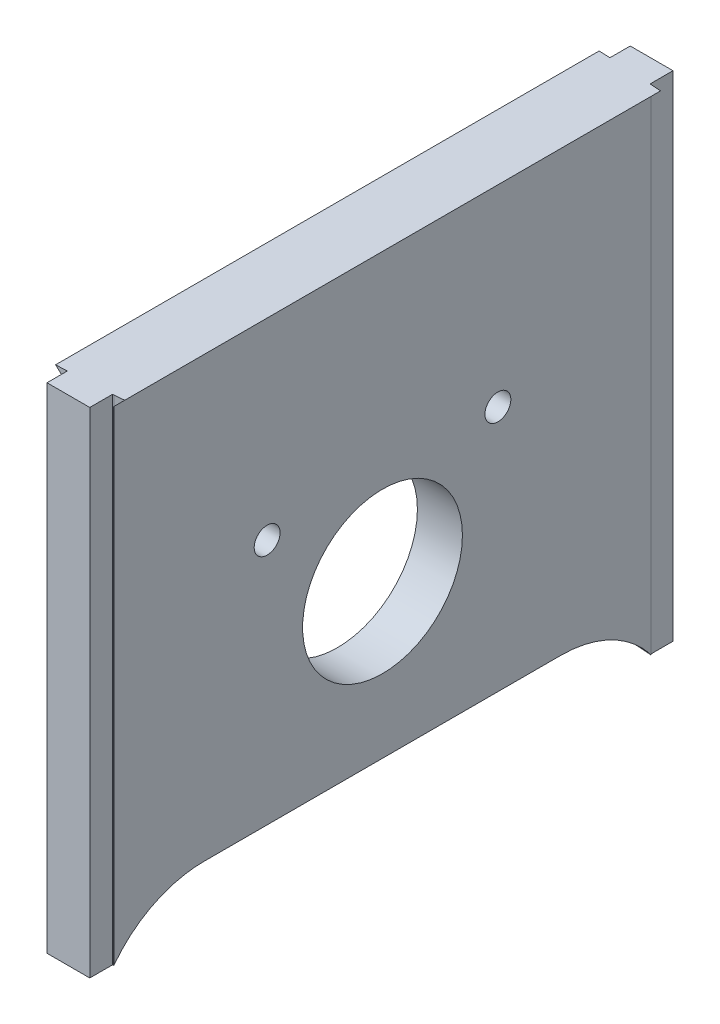
SolidWorks part; units mm, degrees
material "PLA"
ref_plane "Front Plane" through (0, 0, 0) normal (0, 0, 1) x (1, 0, 0)
ref_plane "Top Plane" through (0, 0, 0) normal (0, 1, 0) x (1, 0, 0)
ref_plane "Right Plane" through (0, 0, 0) normal (1, 0, 0) x (0, 0, -1)
sketch "Sketch1" plane through (0, 0, 0) normal (1, 0, 0) x (0, 0, -1)
  line L0 (-17.25, 0) -> (-17.25, -67.25)
  line L1 (17.25, 0) -> (17.25, -67.25)
  line L2 (-17.25, -67.25) -> (17.25, -67.25)
  arc A0 (17.25, 0) -> (-17.25, 0) centre (0, 0) ccw
  circle A1 centre (0, 0) radius 4.1
  circle A2 centre (0, 0) radius 8.125 construction
  circle A3 centre (0, 8.125) radius 1.15
  circle A4 centre (8.125, 0) radius 1.15
  circle A5 centre (-8.125, 0) radius 1.15
  circle A6 centre (0, -8.125) radius 1.15
  dimension "D1" = 34.5
  dimension "D4" = 8.2
  dimension "D5" = 16.25
  dimension "D6" = 2.3
  dimension "D2" = 67.25
  dimension "D3" = 67.25
extrude "Boss-Extrude1" add sketch "Sketch1" along normal blind 3.5
ref_plane "Plane1" through (0, 0, 0) normal (0, -1, 0) x (-1, 0, 0)
ref_plane "Plane2" through (29.7, 0, 0) normal (-1, 0, 0) x (0, 0, 1)
sketch "Sketch2" plane through (0, 0, 0) normal (0, -1, 0) x (-1, 0, 0)
  line L0 (0, -17.25) -> (-59.4, -17.25) construction
  line L1 (-29.7, 0) -> (-29.7, -28) construction
  line L3 (-59.4, -17.25) -> (-59.4, -20.25)
  line L4 (0, -17.25) -> (0, -20.25)
  line L6 (-29.7, -28) -> (-17.6897, -27.7644) construction
  line L7 (-17.6897, -27.7644) -> (-9.1109, -26.529) construction
  line L8 (-9.1109, -26.529) -> (-3.2086, -24.1613) construction
  line L9 (-3.2086, -24.1613) -> (-1.3201, -22.8861) construction
  line L10 (-1.3201, -22.8861) -> (-0.3051, -21.5079) construction
  line L11 (-0.3051, -21.5079) -> (-0.1375, -21.1541) construction
  line L12 (-0.1375, -21.1541) -> (0, -20.25) construction
  line L13 (-3.5, -17.25) -> (-3.7359, -19.9547)
  line L14 (-55.9, -17.25) -> (-55.6641, -19.9547)
  line L15 (-55.9, -17.25) -> (-59.4, -17.25)
  line L17 (0, -17.25) -> (-3.5, -17.25)
  arc A0 (0, -20.25) -> (-1.3201, -22.8861) centre (-4.0147, -19.8881) cw
  arc A1 (-1.3201, -22.8861) -> (-9.1109, -26.529) centre (-11.2153, -11.8765) cw
  arc A2 (-29.7, -28) -> (-9.1109, -26.529) centre (-29.7, 116.8281) ccw
  arc A3 (-29.7, -24.2523) -> (-9.3648, -22.779) centre (-29.7, 116.8281) ccw
  arc A4 (-3.8286, -20.1061) -> (-9.3648, -22.779) centre (-11.2153, -11.8765) cw
  arc A5 (-3.7359, -19.9547) -> (-3.8286, -20.1061) centre (-4.0147, -19.8881) cw
  arc A6 (-29.7, -28) -> (-50.2891, -26.529) centre (-29.7, 116.8281) cw
  arc A7 (-58.0799, -22.8861) -> (-50.2891, -26.529) centre (-48.1847, -11.8765) ccw
  arc A8 (-59.4, -20.25) -> (-58.0799, -22.8861) centre (-55.3853, -19.8881) ccw
  arc A9 (-55.6641, -19.9547) -> (-55.5714, -20.1061) centre (-55.3853, -19.8881) ccw
  arc A10 (-55.5714, -20.1061) -> (-50.0352, -22.779) centre (-48.1847, -11.8765) ccw
  arc A11 (-29.7, -24.2523) -> (-50.0352, -22.779) centre (-29.7, 116.8281) cw
  dimension "D1" = 59.4
extrude "Boss-Extrude2" add sketch "Sketch2" along normal blind 67.25
mirror "Mirror2" about plane through (29.7, 0, 0) normal (-1, 0, 0) of "Boss-Extrude1"
sketch "Sketch3" plane through (0, 0, 0) normal (-1, 0, 0) x (0, 0, 1)
  line L0 (17.25, 0) -> (32.7486, -8.9481)
  line L1 (-1.925, 0) -> (1.925, 0) construction
  line L2 (32.7486, -8.9481) -> (32.7486, 0)
  line L3 (32.7486, 0) -> (17.25, 0)
  arc A0 (17.25, 0) -> (-17.25, 0) centre (0, 0) ccw construction
  dimension "D1" = 30
extrude "Cut-Extrude1" cut sketch "Sketch3" against normal through all
ref_plane "Plane3" through (0, 0, 0) normal (0, 0, -1) x (-1, 0, 0)
mirror "Mirror3" about plane through (0, 0, 0) normal (0, 0, -1) of "Cut-Extrude1", "Boss-Extrude2"
sketch "Sketch4" plane through (0, 0, 0) normal (-1, 0, 0) x (0, 0, 1)
  line L0 (-20.25, -63.75) -> (-20.25, -1.7321) construction
  line L1 (-13.25, -13.5) -> (13.25, -13.5)
  line L2 (-13.25, -13.5) -> (-13.25, -60.75)
  line L3 (-13.25, -60.75) -> (13.25, -60.75)
  line L4 (13.25, -13.5) -> (13.25, -60.75)
  line L5 (20.25, -63.75) -> (20.25, -1.7321) construction
  line L6 (20.25, -67.25) -> (-19.5262, -67.25) construction
  dimension "D1" = 7
  dimension "D2" = 7
  dimension "D3" = 13.5
  dimension "D4" = 6.5
extrude "Cut-Extrude2" cut sketch "Sketch4" against normal blind 3.5
sketch "Sketch6" plane through (0, 0, 0) normal (-1, 0, 0) x (0, 0, 1)
  line L8 (-15.75, -63.25) -> (15.75, -63.25)
  line L9 (-15.75, -11) -> (-15.75, -63.25)
  line L10 (15.75, -63.25) -> (15.75, -11)
  line L11 (15.75, -11) -> (-15.75, -11)
  line L12 (-15.75, -63.25) -> (15.75, -63.25)
  line L13 (-15.75, -11) -> (-15.75, -63.25)
  line L14 (15.75, -63.25) -> (15.75, -11)
  line L15 (15.75, -11) -> (-15.75, -11)
  dimension "D1" = 2.5
extrude "Boss-Extrude3" add sketch "Sketch6" along normal blind 2
chamfer "Chamfer2" distance 2 angle 45 4 edges at (-2, -63.25, 0) (-2, -37.125, 15.75) (-2, -37.125, -15.75) (-2, -11, 0)
sketch "Sketch7" plane through (0, 0, 0) normal (1, 0, 0) x (0, 0, -1)
  line L4 (-13.25, -60.75) -> (13.25, -60.75)
  line L5 (13.25, -60.75) -> (13.25, -13.5)
  line L6 (13.25, -13.5) -> (-13.25, -13.5)
  line L7 (-13.25, -13.5) -> (-13.25, -60.75)
  line L8 (-13.25, -60.75) -> (13.25, -60.75)
  line L9 (13.25, -60.75) -> (13.25, -13.5)
  line L10 (13.25, -13.5) -> (-13.25, -13.5)
  line L11 (-13.25, -13.5) -> (-13.25, -60.75)
  dimension "D1" = 0
extrude "Cut-Extrude3" cut sketch "Sketch7" against normal blind 0.8
sketch "Sketch8" plane through (-2, 0, 0) normal (-1, 0, 0) x (0, 0, 1)
  line L0 (15.75, -63.25) -> (15.75, -11) construction
  line L1 (-10.6511, -32.25) -> (10.75, -32.25)
  line L2 (-10.6511, -32.25) -> (-10.6511, -38.75)
  line L3 (-10.6511, -38.75) -> (10.75, -38.75)
  line L4 (10.75, -32.25) -> (10.75, -38.75)
  line L5 (-15.75, -11) -> (-15.75, -63.25) construction
  line L6 (15.75, -11) -> (7.6086, -11) construction
  line L7 (-15.75, -63.25) -> (15.75, -63.25) construction
  dimension "D1" = 5
  dimension "D2" = 5.0989
  dimension "D3" = 21.25
  dimension "D4" = 24.5
extrude "Cut-Extrude4" cut sketch "Sketch8" against normal up to next
sketch "Sketch9" plane through (59.4, 0, 0) normal (1, 0, 0) x (0, 0, -1)
  circle A0 centre (0, -49.64) radius 7.1
  dimension "D1" = 14.2
extrude "Cut-Extrude5" cut sketch "Sketch9" against normal up to next
ref_plane "Plane4" through (0, -19.75, 0) normal (0, -1, 0) x (-1, 0, 0)
sketch "Sketch10" plane through (0, -19.75, 0) normal (0, -1, 0) x (-1, 0, 0)
  line L0 (-55.6641, -19.9547) -> (-55.9, -17.25) construction
  line L1 (-3.5, -17.25) -> (-3.7359, -19.9547) construction
  line L3 (-3.5, -17.25) -> (-3.5, 17.25) construction
  line L6 (-3.5, 17.25) -> (-3.7359, 19.9547) construction
  line L7 (-55.9, -17.25) -> (-55.9, 17.25) construction
  line L8 (-55.6641, 19.9547) -> (-55.9, 17.25) construction
  line L9 (-55.6641, -19.9547) -> (-55.9, -17.25)
  line L10 (-3.5, -17.25) -> (-3.7359, -19.9547)
  line L11 (-3.5, -17.25) -> (-3.5, -12.56)
  line L12 (-3.5, 17.25) -> (-3.7359, 19.9547)
  line L13 (-55.9, -17.25) -> (-55.9, 17.25)
  line L14 (-55.6641, 19.9547) -> (-55.9, 17.25)
  line L15 (-18.2613, -12.36) -> (-18.2613, -12.56) construction
  line L16 (-12.72, -12.36) -> (-25.62, -12.36) construction
  line L17 (-3.5, -12.56) -> (-34.52, -12.56)
  line L18 (-34.52, -12.56) -> (-34.52, 12.56)
  line L19 (-3.5, 12.56) -> (-3.5, 17.25)
  line L43 (-34.52, 12.56) -> (-3.5, 12.56)
  line L45 (-25.62, 12.36) -> (-12.72, 12.36) construction
  line L46 (-34.52, 5) -> (-34.52, 13.1992) construction
  line L47 (-31.62, 5) -> (-35.82, 5) construction
  line L48 (-34.32, 6.7) -> (-34.32, 5.6557) construction
  arc A0 (-55.6641, -19.9547) -> (-55.5714, -20.1061) centre (-55.3853, -19.8881) ccw construction
  arc A1 (-50.0352, -22.779) -> (-9.3648, -22.779) centre (-29.7, 116.8281) ccw construction
  arc A2 (-55.5714, -20.1061) -> (-50.0352, -22.779) centre (-48.1847, -11.8765) ccw construction
  arc A3 (-9.3648, -22.779) -> (-3.8286, -20.1061) centre (-11.2153, -11.8765) ccw construction
  arc A4 (-3.8286, -20.1061) -> (-3.7359, -19.9547) centre (-4.0147, -19.8881) ccw construction
  arc A5 (-3.7359, 19.9547) -> (-3.8286, 20.1061) centre (-4.0147, 19.8881) ccw construction
  arc A6 (-3.8286, 20.1061) -> (-9.3648, 22.779) centre (-11.2153, 11.8765) ccw construction
  arc A7 (-9.3648, 22.779) -> (-50.0352, 22.779) centre (-29.7, -116.8281) ccw construction
  arc A8 (-55.5714, 20.1061) -> (-55.6641, 19.9547) centre (-55.3853, 19.8881) ccw construction
  arc A9 (-50.0352, 22.779) -> (-55.5714, 20.1061) centre (-48.1847, 11.8765) ccw construction
  arc A30 (-55.6641, -19.9547) -> (-55.5714, -20.1061) centre (-55.3853, -19.8881) ccw
  arc A31 (-50.0352, -22.779) -> (-9.3648, -22.779) centre (-29.7, 116.8281) ccw
  arc A32 (-55.5714, -20.1061) -> (-50.0352, -22.779) centre (-48.1847, -11.8765) ccw
  arc A33 (-9.3648, -22.779) -> (-3.8286, -20.1061) centre (-11.2153, -11.8765) ccw
  arc A34 (-3.8286, -20.1061) -> (-3.7359, -19.9547) centre (-4.0147, -19.8881) ccw
  arc A35 (-3.7359, 19.9547) -> (-3.8286, 20.1061) centre (-4.0147, 19.8881) ccw
  arc A36 (-3.8286, 20.1061) -> (-9.3648, 22.779) centre (-11.2153, 11.8765) ccw
  arc A37 (-9.3648, 22.779) -> (-50.0352, 22.779) centre (-29.7, -116.8281) ccw
  arc A38 (-55.5714, 20.1061) -> (-55.6641, 19.9547) centre (-55.3853, 19.8881) ccw
  arc A39 (-50.0352, 22.779) -> (-55.5714, 20.1061) centre (-48.1847, 11.8765) ccw
  dimension "D1" = 0.2
  dimension "D2" = 0.2
  dimension "D3" = 0.2
extrude "Boss-Extrude4" add sketch "Sketch10" along normal blind 3.5
sketch "Sketch11" plane through (0, -23.25, 0) normal (0, -1, 0) x (-1, 0, 0)
  line L0 (-36.07, -6.9) -> (-40.07, -6.9) construction
  line L2 (-36.07, -6.9) -> (-36.07, -24.1084) construction
  line L3 (-40.07, -6.9) -> (-40.07, -24.1084) construction
  line L5 (-36.07, -24.1084) -> (-40.07, -24.1084)
  line L6 (-36.07, -24.1084) -> (-36.07, 25.609)
  line L7 (-36.07, 25.609) -> (-40.07, 25.609)
  line L8 (-40.07, -24.1084) -> (-40.07, 25.609)
  arc A0 (-50.0352, -22.779) -> (-41.07, -23.7934) centre (-29.7, 116.8281) ccw construction
  dimension "D1" = 4
extrude "Boss-Extrude5" add sketch "Sketch11" along normal blind 40
sketch "Sketch12" plane through (40.07, 0, 0) normal (1, 0, 0) x (0, 0, -1)
  circle A0 centre (0, -49.64) radius 7.1
extrude "Cut-Extrude6" cut sketch "Sketch12" against normal blind 10
chamfer "Chamfer3" distance 1 angle 45 1 edges at (36.07, -23.25, 0)
chamfer "Chamfer4" distance 1 angle 45 1 edges at (40.07, -23.25, 0)
sketch "Sketch13" plane through (59.4, 0, 0) normal (1, 0, 0) x (0, 0, -1)
  circle A0 centre (0, -49.64) radius 9
  circle A1 centre (0, -49.64) radius 5.5
  dimension "D1" = 18
  dimension "D2" = 11
extrude "Boss-Extrude6" add sketch "Sketch13" along normal blind 1.5
sketch "Sketch16" plane through (60.9, 0, 0) normal (1, 0, 0) x (0, 0, -1)
  circle A0 centre (0, -49.64) radius 9
extrude "Boss-Extrude7" add sketch "Sketch16" along normal blind 1
fillet "Fillet2" radius 1 1 edges at (61.9, -49.64, -9)
ref_plane "Plane5" through (0, 0, 20.25) normal (0, 0, -1) x (-1, 0, 0)
sketch "Sketch17" plane through (0, 0, 20.25) normal (0, 0, -1) x (-1, 0, 0)
  line L0 (-59.4, -67.25) -> (-55.9, -67.25) construction
  line L1 (-59.4, -67.25) -> (-59.4, -70.75) construction
  line L3 (-55.9, -67.25) -> (-59.4, -70.75) construction
  line L4 (-59.4, -67.25) -> (-59.65, -67.25) construction
  line L5 (-59.4, -70.75) -> (-59.65, -71) construction
  line L6 (-59.65, -71) -> (-59.65, -105.91) construction
  line L7 (-59.4, -67.25) -> (-59.4, -63.75) construction
  line L8 (-59.4, -63.75) -> (-64.5645, -68.9145) construction
  line L9 (-59.65, -105.91) -> (-63.15, -105.91)
  line L10 (-63.15, -105.91) -> (-63.15, -67.5)
  line L11 (-63.15, -67.5) -> (-59.4, -63.75)
  line L12 (-59.4, -63.75) -> (-59.4, -67.25)
  line L13 (-59.4, -67.25) -> (-55.9, -67.25)
  line L14 (-55.9, -67.25) -> (-59.65, -71)
  line L15 (-59.65, -71) -> (-59.65, -105.91)
  dimension "D1" = 3.5
  dimension "D2" = 3.5
  dimension "D3" = 0.25
  dimension "D4" = 3.5
  dimension "D5" = 45
  dimension "D6" = 3.5
sketch "Sketch18" plane through (55.9, 0, 0) normal (-1, 0, 0) x (0, 0, 1)
  circle A0 centre (0, -49.64) radius 9
  circle A1 centre (0, -49.64) radius 7.1
  circle A2 centre (0, -49.64) radius 7.1
  dimension "D2" = 18
  dimension "D1" = 0
extrude "Boss-Extrude8" add sketch "Sketch18" along normal blind 0.5
chamfer "Chamfer5" distance 0.5 angle 45 1 edges at (55.9, -49.64, 9)
extrude "Boss-Extrude9" add sketch "Sketch17" along normal blind 40.5
sketch "Sketch19" plane through (63.15, 0, 0) normal (1, 0, 0) x (0, 0, -1)
  line L0 (-17.7, -88.21) -> (-20.25, -85.66)
  line L1 (-20.25, -85.66) -> (-20.25, -105.91)
  line L2 (20.25, -105.91) -> (-20.25, -105.91) construction
  line L3 (0, -105.91) -> (0, -88.21) construction
  line L4 (-20.25, -67.5) -> (-20.25, -105.91) construction
  line L5 (17.7, -88.21) -> (20.25, -85.66)
  line L6 (-20.25, -105.91) -> (0, -105.91)
  line L7 (20.25, -67.5) -> (20.25, -105.91) construction
  line L8 (0, -105.91) -> (20.25, -105.91)
  line L9 (20.25, -105.91) -> (20.25, -85.66)
  arc A0 (-17.7, -88.21) -> (17.7, -88.21) centre (0, -88.21) ccw
  line M5 (-20.25, -67.5) -> (-20.25, -105.91)
  line M6 (-20.25, -105.91) -> (20.25, -105.91)
  line M7 (20.25, -105.91) -> (20.25, -67.5)
  dimension "D1" = 17.7
  dimension "D2" = 45
  dimension "D3" = 45
extrude "Cut-Extrude8" cut sketch "Sketch19" against normal up to next contours A0 L0 M5 M6 | A0 L5 M6 M7
chamfer "Chamfer6" distance 1.5 angle 45 1 edges at (59.4, -49.64, 9)
sketch "Sketch20" plane through (63.15, 0, 0) normal (1, 0, 0) x (0, 0, -1)
  line L0 (0, -49.64) -> (0, -88.21) construction
  circle A0 centre (0, -88.21) radius 7.1
  dimension "D2" = 14.2
  dimension "D1" = 38.57
extrude "Cut-Extrude9" cut sketch "Sketch20" against normal up to next
sketch "Sketch21" plane through (0, 0, 0) normal (-1, 0, 0) x (0, 0, 1)
  circle A0 centre (0, 8.125) radius 1.5
  circle A1 centre (8.125, 0) radius 1.5
  circle A2 centre (0, -8.125) radius 1.5
  circle A3 centre (-8.125, 0) radius 1.5
  dimension "D1" = 3
extrude "Boss-Extrude10" add sketch "Sketch21" against normal blind 3.5
mirror "Mirror4" about plane through (29.7, 0, 0) normal (-1, 0, 0) of "Cut-Extrude9", "Cut-Extrude8", "Boss-Extrude9"
sketch "Sketch22" plane through (-2, 0, 0) normal (-1, 0, 0) x (0, 0, 1)
  circle A0 centre (0, -49.64) radius 3.75
  dimension "D1" = 7.5
extrude "Cut-Extrude10" cut sketch "Sketch22" against normal up to next
sketch "Sketch23" plane through (-0.8, 0, 0) normal (1, 0, 0) x (0, 0, -1)
  line L65 (10.8, -38.89) -> (7, -38.89)
  line L66 (10.8, -32.115) -> (10.8, -38.89)
  line L67 (9.303, -32.115) -> (10.8, -32.115)
  line L68 (9.4423, -31.8921) -> (9.303, -32.115)
  line L69 (9.4423, -20.9369) -> (9.4423, -31.8921)
  line L70 (-8.2423, -19.7369) -> (8.2423, -19.7369)
  line L71 (-9.4423, -31.8921) -> (-9.4423, -20.9369)
  line L72 (-9.303, -32.115) -> (-9.4423, -31.8921)
  line L73 (-10.8, -32.115) -> (-9.303, -32.115)
  line L74 (-10.8, -38.89) -> (-10.8, -32.115)
  line L75 (-7, -38.89) -> (-10.8, -38.89)
  line L76 (-7, -40.6536) -> (-7, -38.89)
  line L77 (-11.36, -43.6785) -> (-9.7065, -43.6785)
  line L78 (-11.86, -16.5298) -> (-11.86, -43.1785)
  line L79 (10.3601, -15.03) -> (-10.3604, -15.03)
  line L80 (11.86, -43.1784) -> (11.86, -16.5295)
  line L81 (9.7065, -43.6785) -> (11.36, -43.6785)
  line L82 (7, -38.89) -> (7, -40.6536)
  line L83 (10.8, -38.89) -> (7, -38.89)
  line L84 (10.8, -32.115) -> (10.8, -38.89)
  line L85 (9.303, -32.115) -> (10.8, -32.115)
  line L86 (9.4423, -31.8921) -> (9.303, -32.115)
  line L87 (9.4423, -20.9369) -> (9.4423, -31.8921)
  line L88 (-8.2423, -19.7369) -> (8.2423, -19.7369)
  line L89 (-9.4423, -31.8921) -> (-9.4423, -20.9369)
  line L90 (-9.303, -32.115) -> (-9.4423, -31.8921)
  line L91 (-10.8, -32.115) -> (-9.303, -32.115)
  line L92 (-10.8, -38.89) -> (-10.8, -32.115)
  line L93 (-7, -38.89) -> (-10.8, -38.89)
  line L94 (-7, -40.6536) -> (-7, -38.89)
  line L95 (-11.36, -43.6785) -> (-9.7065, -43.6785)
  line L96 (-11.86, -16.5298) -> (-11.86, -43.1785)
  line L97 (10.3601, -15.03) -> (-10.3604, -15.03)
  line L98 (11.86, -43.1784) -> (11.86, -16.5295)
  line L99 (9.7065, -43.6785) -> (11.36, -43.6785)
  line L100 (7, -38.89) -> (7, -40.6536)
  circle A28 centre (-10.25, -16.89) radius 1.15
  circle A29 centre (10.25, -16.89) radius 1.15
  circle A30 centre (10.25, -41.34) radius 1.15
  circle A31 centre (-10.25, -41.34) radius 1.15
  arc A40 (9.4423, -20.9369) -> (8.2423, -19.7369) centre (8.2423, -20.9369) ccw
  arc A41 (-8.2423, -19.7369) -> (-9.4423, -20.9369) centre (-8.2423, -20.9369) ccw
  arc A42 (-7, -40.6536) -> (-9.7065, -43.6785) centre (0, -49.64) ccw
  arc A43 (-11.86, -43.1785) -> (-11.36, -43.6785) centre (-11.36, -43.1785) ccw
  arc A44 (11.36, -43.6785) -> (11.86, -43.1784) centre (11.36, -43.1785) ccw
  arc A45 (9.7065, -43.6785) -> (7, -40.6536) centre (0, -49.64) ccw
  arc A46 (9.4423, -20.9369) -> (8.2423, -19.7369) centre (8.2423, -20.9369) ccw
  arc A47 (-8.2423, -19.7369) -> (-9.4423, -20.9369) centre (-8.2423, -20.9369) ccw
  arc A48 (-7, -40.6536) -> (-9.7065, -43.6785) centre (0, -49.64) ccw
  arc A49 (-11.86, -43.1785) -> (-11.36, -43.6785) centre (-11.36, -43.1785) ccw
  arc A50 (11.36, -43.6785) -> (11.86, -43.1784) centre (11.36, -43.1785) ccw
  arc A51 (9.7065, -43.6785) -> (7, -40.6536) centre (0, -49.64) ccw
  spline S4 degree 3 poles (876.1919, -4935.4211) (64.4065, -262.5595) (5.2732, -11.8772) (-10.7484, -15.0781) (-10.8437, -15.1068) (-11.0252, -15.182) (-11.1112, -15.2282) (-11.2742, -15.337) (-11.3514, -15.4001) (-11.5587, -15.6075) (-11.6705, -15.7746) (-16.8246, -28.2046) (137.8576, -116.0941) (2240.6366, 4442.549) knots -20.656549 -20.656549 -20.656549 -20.656549 0.125 0.125 0.25 0.25 0.375 0.375 0.5 0.5 0.75 0.75 17.73694 17.73694 17.73694 17.73694 only from (-10.3604, -15.03) to (-11.86, -16.5298)
  spline S5 degree 3 poles (-4908.42, -903.1905) (-235.6796, -91.3054) (15.0132, -32.1634) (11.8119, -16.1415) (11.7831, -16.0463) (11.708, -15.8648) (11.6618, -15.7788) (11.553, -15.6158) (11.4898, -15.5386) (11.2825, -15.3312) (11.1153, -15.2194) (-1.3149, -10.0656) (-89.2028, -164.7553) (4469.6821, -2267.1355) knots -20.657077 -20.657077 -20.657077 -20.657077 0.125 0.125 0.25 0.25 0.375 0.375 0.5 0.5 0.75 0.75 17.737176 17.737176 17.737176 17.737176 only from (11.86, -16.5295) to (10.3601, -15.03)
  spline S6 degree 3 poles (-10.3604, -15.03) (-10.4595, -15.0298) (-10.5568, -15.0398) (-10.7484, -15.0781) (-10.8437, -15.1068) (-11.0252, -15.182) (-11.1112, -15.2282) (-11.2742, -15.337) (-11.3514, -15.4001) (-11.5587, -15.6075) (-11.6705, -15.7746) (-11.82, -16.1352) (-11.8602, -16.3318) (-11.86, -16.5298) knots 0 0 0 0 0.125 0.125 0.25 0.25 0.375 0.375 0.5 0.5 0.75 0.75 1 1 1 1
  spline S7 degree 3 poles (11.86, -16.5295) (11.8602, -16.4305) (11.8502, -16.3331) (11.8119, -16.1415) (11.7831, -16.0463) (11.708, -15.8648) (11.6618, -15.7788) (11.553, -15.6158) (11.4898, -15.5386) (11.2825, -15.3312) (11.1153, -15.2194) (10.7548, -15.0699) (10.5581, -15.0298) (10.3601, -15.03) knots 0 0 0 0 0.125 0.125 0.25 0.25 0.375 0.375 0.5 0.5 0.75 0.75 1 1 1 1
  dimension "D2" = 2.3
  dimension "D3" = 2.3
  dimension "D4" = 2.3
  dimension "D5" = 2.3
  dimension "D1" = 0.2
extrude "Boss-Extrude11" add sketch "Sketch23" along normal offset from surface (1.82 mm away) 0.2
sketch "Sketch24" plane through (36.07, 0, 0) normal (-1, 0, 0) x (0, 0, 1)
  line L1 (-13, -29.275) -> (-8, -29.275)
  line L2 (-13, -29.275) -> (-13, -45.2091)
  line L3 (-13, -45.2091) -> (-8, -45.2091)
  line L4 (-8, -29.275) -> (-8, -45.2091)
  line L5 (8, -29.275) -> (13, -29.275)
  line L6 (8, -29.275) -> (8, -45.2091)
  line L7 (8, -45.2091) -> (13, -45.2091)
  line L8 (13, -29.275) -> (13, -45.2091)
  circle A0 centre (-10.25, -41.34) radius 1.15
  circle A9 centre (10.25, -41.34) radius 1.15
  dimension "D5" = 2.3
  dimension "D6" = 2.3
  dimension "D1" = 5
  dimension "D2" = 13
  dimension "D3" = 13
  dimension "D4" = 5
extrude "Boss-Extrude12" add sketch "Sketch24" along a picked direction on the side of the normal up to next (2.65 mm away)
sketch "Sketch25" plane through (36.07, 0, 0) normal (-1, 0, 0) x (0, 0, 1)
  circle A4 centre (10.25, -41.34) radius 1.15 construction
  circle A5 centre (-10.25, -41.34) radius 1.15 construction
  circle A6 centre (10.25, -41.34) radius 1.15
  circle A7 centre (-10.25, -41.34) radius 1.15
extrude "Cut-Extrude11" cut sketch "Sketch25" against normal up to next
sketch "Sketch26" plane through (0, 0, 0) normal (-1, 0, 0) x (0, 0, 1)
  circle A1 centre (0, 0) radius 13.375
  dimension "D1" = 26.75
extrude "Cut-Extrude12" cut sketch "Sketch26" along normal blind 3.3
sketch "Sketch27" plane through (-2, 0, 0) normal (-1, 0, 0) x (0, 0, 1)
  circle A0 centre (0, -49.64) radius 5
  dimension "D1" = 10
extrude "Boss-Extrude13" add sketch "Sketch27" along normal blind 1
fillet "Fillet7" radius 0.75 1 edges at (-3, -49.64, 5)
sketch "Sketch28" plane through (3.5, 0, 0) normal (1, 0, 0) x (0, 0, -1)
  circle A0 centre (0, 0) radius 4.1
  circle A1 centre (0, 0) radius 8
  dimension "D1" = 8.2
  dimension "D2" = 16
extrude "Boss-Extrude14" add sketch "Sketch28" along normal blind 1.5
sketch "Sketch29" plane through (5, 0, 0) normal (1, 0, 0) x (0, 0, -1)
  circle A0 centre (0, 0) radius 4.1
  circle A1 centre (0, 0) radius 8
  dimension "D1" = 8.2
  dimension "D2" = 16
extrude "Boss-Extrude15" add sketch "Sketch29" along normal blind 8.5
sketch "Sketch30" plane through (0, 0, 0) normal (0, -1, 0) x (-1, 0, 0)
  line L0 (-13.5, 0) -> (-3.5, 0) construction
  line L1 (-13.5, 8) -> (-13.5, -8) construction
  circle A0 centre (-8.5, 0) radius 1.125
  dimension "D2" = 2.25
  dimension "D1" = 10
extrude "Cut-Extrude13" cut sketch "Sketch30" against normal through all and the other way blind 15
sketch "Sketch31" plane through (-3.75, 0, 0) normal (-1, 0, 0) x (0, 0, 1)
  line L5 (-20.25, -85.66) -> (-17.7, -88.21)
  line L6 (17.7, -88.21) -> (20.25, -85.66)
  line L7 (20.25, -85.66) -> (20.25, -67.5)
  line L8 (20.25, -67.5) -> (-20.25, -67.5)
  line L9 (-20.25, -67.5) -> (-20.25, -85.66)
  line L10 (-20.25, -85.66) -> (-17.7, -88.21)
  line L11 (17.7, -88.21) -> (20.25, -85.66)
  line L12 (20.25, -85.66) -> (20.25, -67.5)
  line L13 (20.25, -67.5) -> (-20.25, -67.5)
  line L14 (-20.25, -67.5) -> (-20.25, -85.66)
  circle A0 centre (0, -88.21) radius 7.1 construction
  arc A1 (-17.7, -88.21) -> (17.7, -88.21) centre (0, -88.21) ccw
  arc A2 (-17.7, -88.21) -> (17.7, -88.21) centre (0, -88.21) ccw
  circle A3 centre (0, -88.21) radius 7.1
  circle M7 centre (0, -88.21) radius 7.1
  line M8 (-20.25, -85.66) -> (-17.7, -88.21)
  arc M9 (-17.7, -88.21) -> (17.7, -88.21) centre (0, -88.21) ccw
  line M10 (17.7, -88.21) -> (20.25, -85.66)
  line M11 (20.25, -85.66) -> (20.25, -67.5)
  line M12 (20.25, -67.5) -> (-20.25, -67.5)
  line M13 (-20.25, -67.5) -> (-20.25, -85.66)
  dimension "D1" = 0
extrude "Boss-Extrude16" add sketch "Sketch31" along normal blind 0.5 contours M13 M8 M9 M10 M11 M12 M7
chamfer "Chamfer7" distance 0.5 angle 45 3 edges at (-4, -67.5, -20.25) (-4, -67.5, 20.25) (-4.25, -67.5, 0)
ref_plane "Plane6" through (29.7, 0, 0) normal (1, 0, 0) x (0, 0, -1)
mirror "Mirror5" about plane through (29.7, 0, 0) normal (1, 0, 0) of "Chamfer7", "Boss-Extrude16"
fillet "Fillet8" radius 2.5 4 edges at (59.65, -71, 0) (-0.25, -71, 0) (-4.25, -68, 0) (63.65, -68, 0)
sketch "Sketch32" plane through (59.4, 0, 0) normal (1, 0, 0) x (0, 0, -1)
  line L0 (20.25, -63.75) -> (-20.25, -63.75) construction
  line L1 (-15.25, -38.03) -> (15.25, -38.03)
  line L2 (-15.25, -38.03) -> (-15.25, -61.25)
  line L3 (-15.25, -61.25) -> (15.25, -61.25)
  line L4 (15.25, -38.03) -> (15.25, -61.25)
  line L5 (20.25, -63.75) -> (20.25, -1.7321) construction
  line L6 (-20.25, -32.67) -> (-20.25, 32.67) construction
  dimension "D1" = 2.5
  dimension "D2" = 5
  dimension "D3" = 5
  dimension "D4" = 23.22
extrude "Cut-Extrude14" cut sketch "Sketch32" against normal blind 10 and the other way blind 10
fillet "Fillet9" radius 5 4 edges at (57.65, -61.25, -15.25) (57.65, -61.25, 15.25) (57.65, -38.03, 15.25) (57.65, -38.03, -15.25)
sketch "Sketch33" plane through (59.4, 0, 0) normal (1, 0, 0) x (0, 0, -1)
  line L5 (-18.25, -56.25) -> (-16.75, -56.25)
  line L6 (16.75, -56.25) -> (18.25, -56.25)
  line L8 (16.75, -56.25) -> (16.75, -43.03)
  line L9 (10.25, -36.53) -> (-10.25, -36.53)
  line L10 (-16.75, -43.03) -> (-16.75, -56.25)
  line L11 (16.75, -56.25) -> (16.75, -43.03)
  line L12 (10.25, -36.53) -> (-10.25, -36.53)
  line L13 (-16.75, -43.03) -> (-16.75, -56.25)
  line L36 (18.25, -56.25) -> (18.25, -43.03)
  line L37 (10.25, -35.03) -> (-10.25, -35.03)
  line L38 (-18.25, -43.03) -> (-18.25, -56.25)
  line L39 (18.25, -56.25) -> (18.25, -43.03)
  line L40 (10.25, -35.03) -> (-10.25, -35.03)
  line L41 (-18.25, -43.03) -> (-18.25, -56.25)
  arc A6 (16.75, -43.03) -> (10.25, -36.53) centre (10.25, -43.03) ccw
  arc A7 (-10.25, -36.53) -> (-16.75, -43.03) centre (-10.25, -43.03) ccw
  arc A8 (16.75, -43.03) -> (10.25, -36.53) centre (10.25, -43.03) ccw
  arc A9 (-10.25, -36.53) -> (-16.75, -43.03) centre (-10.25, -43.03) ccw
  arc A28 (18.25, -43.03) -> (10.25, -35.03) centre (10.25, -43.03) ccw
  arc A29 (-10.25, -35.03) -> (-18.25, -43.03) centre (-10.25, -43.03) ccw
  arc A30 (18.25, -43.03) -> (10.25, -35.03) centre (10.25, -43.03) ccw
  arc A31 (-10.25, -35.03) -> (-18.25, -43.03) centre (-10.25, -43.03) ccw
  dimension "D1" = 3
  dimension "D2" = 1.5
extrude "Cut-Extrude15" cut sketch "Sketch33" against normal blind 2
sketch "Sketch34" plane through (59.4, 0, 0) normal (1, 0, 0) x (0, 0, -1)
  circle A10 centre (0, 8.125) radius 2.25
  circle A11 centre (8.125, 0) radius 2.25
  circle A12 centre (0, -8.125) radius 2.25
  circle A13 centre (-8.125, 0) radius 2.25
  dimension "D1" = 4.5
  dimension "D2" = 4.5
  dimension "D3" = 4.5
  dimension "D4" = 4.5
extrude "Cut-Extrude16" cut sketch "Sketch34" against normal blind 1.5
sketch "Sketch35" plane through (0, 0, 20.25) normal (0, 0, 1) x (1, 0, 0)
  line L0 (40.65, 17.25) -> (40.65, -17.25) construction
  line L1 (40.65, 2) -> (55.65, 2)
  line L2 (40.65, 2) -> (40.65, -19.75)
  line L3 (40.65, -19.75) -> (55.65, -19.75)
  line L4 (55.65, 2) -> (55.65, -19.75)
  line L5 (55.65, -17.25) -> (55.65, 17.25) construction
  line L6 (55.9, 0) -> (59.4, 0) construction
  dimension "D1" = 2
  dimension "D2" = 21.75
extrude "Cut-Extrude17" cut sketch "Sketch35" along normal through all and the other way blind 2
fillet "Fillet10" radius 1 2 edges at (40.65, -12.8586, 27.5855) (55.65, -12.0138, 24.6591)
fillet "Fillet11" radius 1 1 edges at (40.65, -11.7735, 23.8267)
sketch "Sketch36" plane through (1.02, 0, 0) normal (1, 0, 0) x (0, 0, -1)
  circle A8 centre (10.25, -41.34) radius 1.15 construction
  circle A9 centre (10.25, -16.89) radius 1.15 construction
  circle A10 centre (-10.25, -16.89) radius 1.15 construction
  circle A11 centre (-10.25, -41.34) radius 1.15 construction
  circle A12 centre (10.25, -41.34) radius 1.15
  circle A13 centre (10.25, -16.89) radius 1.15
  circle A14 centre (-10.25, -16.89) radius 1.15
  circle A15 centre (-10.25, -41.34) radius 1.15
extrude "Cut-Extrude18" cut sketch "Sketch36" against normal through all
sketch "Sketch39" plane through (0, -63.25, 0) normal (0, -1, 0) x (1, 0, 0)
  line L5 (63.65, -17.7) -> (63.65, 17.7) construction
  line L6 (31.9354, -24.2346) -> (31.9354, 24.2346)
  line L10 (-40.6675, 54.8541) -> (88.4301, 54.8541)
  line L11 (-40.6675, 54.8541) -> (-40.6675, -35.7578)
  line L12 (-40.6675, -35.7578) -> (88.4301, -35.7578)
  line L13 (88.4301, 54.8541) -> (88.4301, -35.7578)
  line L14 (41.1443, -23.7873) -> (41.1443, 23.7873)
  line L15 (36.07, 24.1084) -> (36.07, 26.0079)
  line L16 (36.07, 26.0079) -> (40.07, 26.0079)
  line L17 (40.07, 23.8706) -> (40.07, 26.0079)
  line L18 (38.07, 26.0079) -> (38.07, 27.7579) construction
  line L19 (31.9354, 0) -> (8.5, 0) construction
  line L20 (36.07, -24.1084) -> (36.07, -26.0079)
  line L21 (36.07, -26.0079) -> (40.07, -26.0079)
  line L22 (40.07, -23.8706) -> (40.07, -26.0079)
  line L23 (38.07, -26.0079) -> (38.07, -27.7579) construction
  line L24 (41.1443, 0) -> (63.65, 0) construction
  circle A4 centre (8.5, 0) radius 1.125 construction
  circle A5 centre (8.5, 0) radius 1.125 construction
  arc A6 (31.9354, -24.2346) -> (36.07, -24.1084) centre (29.7, 116.8281) ccw
  arc A7 (41.1443, 23.7873) -> (40.07, 23.8706) centre (29.7, -116.8281) ccw
  arc A8 (36.07, 24.1084) -> (31.9354, 24.2346) centre (29.7, -116.8281) ccw
  arc A9 (40.07, -23.8706) -> (41.1443, -23.7873) centre (29.7, 116.8281) ccw
  point P3 (63.65, 0)
  dimension "D1" = 1.75
  dimension "D2" = 1.75
extrude "Cut-Extrude24" cut sketch "Sketch39" against normal through all and the other way through all
sketch "Sketch40" plane through (0, -19.75, 0) normal (0, 1, 0) x (1, 0, 0)
  line L1 (11.6391, 42.1834) -> (66.5641, 42.1834)
  line L2 (11.6391, 42.1834) -> (11.6391, -29.5655)
  line L3 (11.6391, -29.5655) -> (66.5641, -29.5655)
  line L4 (66.5641, 42.1834) -> (66.5641, -29.5655)
extrude "Cut-Extrude25" cut sketch "Sketch40" against normal up to surface (3.5 mm away) and the other way through all up to face at (33.3652, -23.25, 0)
sketch "Sketch41" plane through (0, -23.25, 0) normal (0, 1, 0) x (1, 0, 0)
  line L0 (36.07, -24.1084) -> (36.17, -24.1039)
  line L1 (40.07, -23.8706) -> (39.97, -23.878)
  line L8 (36.07, 24.1084) -> (36.17, 24.1039)
  line L9 (40.07, 23.8706) -> (39.97, 23.878)
  line L12 (40.07, 23.8706) -> (40.07, 26.0079)
  line L13 (40.07, 26.0079) -> (36.07, 26.0079)
  line L14 (36.07, 26.0079) -> (36.07, 24.1084)
  line L15 (35.07, 24.15) -> (35.07, -24.15)
  line L16 (39.97, 23.7777) -> (39.97, 25.9079)
  line L17 (39.97, 25.9079) -> (36.17, 25.9079)
  line L18 (36.17, 25.9079) -> (36.17, 24.0037)
  line L19 (35.17, 24.0461) -> (35.17, -24.0461)
  line L20 (36.17, -24.0037) -> (36.17, -25.9079)
  line L21 (36.17, -25.9079) -> (39.97, -25.9079)
  line L22 (39.97, -25.9079) -> (39.97, -23.7777)
  line L23 (40.97, -23.7011) -> (40.97, 23.7011)
  line L24 (39.97, 23.878) -> (39.97, 25.9079)
  line L25 (39.97, 25.9079) -> (36.17, 25.9079)
  line L26 (36.17, 25.9079) -> (36.17, 24.1039)
  line L28 (36.17, -24.1039) -> (36.17, -25.9079)
  line L29 (36.17, -25.9079) -> (39.97, -25.9079)
  line L30 (39.97, -25.9079) -> (39.97, -23.878)
  line L32 (36.07, -24.1084) -> (36.07, -26.0079)
  line L33 (36.07, -26.0079) -> (40.07, -26.0079)
  line L34 (40.07, -26.0079) -> (40.07, -23.8706)
  line L35 (41.07, -23.7934) -> (41.07, 23.7934)
  line L36 (40.07, 23.8706) -> (40.07, 26.0079)
  line L37 (40.07, 26.0079) -> (36.07, 26.0079)
  line L38 (36.07, 26.0079) -> (36.07, 24.1084)
  line L40 (36.07, -24.1084) -> (36.07, -26.0079)
  line L41 (36.07, -26.0079) -> (40.07, -26.0079)
  line L42 (40.07, -26.0079) -> (40.07, -23.8706)
  arc A0 (35.07, -24.15) -> (36.07, -24.1084) centre (29.7, 116.8281) ccw construction
  arc A1 (40.07, -23.8706) -> (41.07, -23.7934) centre (29.7, 116.8281) ccw construction
  arc A2 (36.07, 24.1084) -> (35.07, 24.15) centre (29.7, -116.8281) ccw construction
  arc A3 (41.07, 23.7934) -> (40.07, 23.8706) centre (29.7, -116.8281) ccw construction
  arc A5 (41.07, 23.7934) -> (40.07, 23.8706) centre (29.7, -116.8281) ccw
  arc A6 (36.07, 24.1084) -> (35.07, 24.15) centre (29.7, -116.8281) ccw
  arc A7 (35.07, -24.15) -> (36.07, -24.1084) centre (29.7, 116.8281) ccw
  arc A8 (40.97, 23.7011) -> (39.97, 23.7777) centre (29.7, -116.8281) ccw
  arc A9 (36.17, 24.0037) -> (35.17, 24.0461) centre (29.7, -116.8281) ccw
  arc A10 (35.17, -24.0461) -> (36.17, -24.0037) centre (29.7, 116.8281) ccw
  arc A11 (39.97, -23.7777) -> (40.97, -23.7011) centre (29.7, 116.8281) ccw
  arc A16 (40.07, -23.8706) -> (41.07, -23.7934) centre (29.7, 116.8281) ccw
  dimension "D1" = 0.1
  dimension "D3" = 0
extrude "Cut-Extrude26" cut sketch "Sketch41" against normal through all
fillet "Fillet12" radius 10 2 edges at (38.0708, -63.25, -24.0037) (38.0708, -63.25, 24.0037)
sketch "Sketch42" plane through (0, -23.25, 0) normal (0, 1, 0) x (1, 0, 0)
  line L12 (40.07, 23.8706) -> (39.97, 23.878)
  line L13 (39.97, 23.878) -> (39.97, 25.9079)
  line L14 (39.97, 25.9079) -> (36.17, 25.9079)
  line L15 (36.17, 25.9079) -> (36.17, 24.1039)
  line L16 (36.17, 24.1039) -> (36.07, 24.1084)
  line L17 (35.07, 24.15) -> (35.07, -24.15)
  line L18 (36.07, -24.1084) -> (36.17, -24.1039)
  line L19 (36.17, -24.1039) -> (36.17, -25.9079)
  line L20 (36.17, -25.9079) -> (39.97, -25.9079)
  line L21 (39.97, -25.9079) -> (39.97, -23.878)
  line L22 (36.07, -24.1084) -> (36.17, -24.1039)
  line L23 (41.07, -23.7934) -> (41.07, 23.7934)
  line L24 (40.07, 23.8706) -> (39.97, 23.878)
  line L25 (39.97, 23.878) -> (39.97, 25.9079)
  line L26 (39.97, 25.9079) -> (36.17, 25.9079)
  line L27 (36.17, 25.9079) -> (36.17, 24.1039)
  line L28 (36.17, 24.1039) -> (36.07, 24.1084)
  line L29 (35.07, 24.15) -> (35.07, -24.15)
  line L31 (36.17, -24.1039) -> (36.17, -25.9079)
  line L32 (36.17, -25.9079) -> (39.97, -25.9079)
  line L33 (39.97, -25.9079) -> (39.97, -23.878)
  line L35 (41.07, -23.7934) -> (41.07, 23.7934)
  line L36 (39.97, -23.878) -> (40.07, -23.8706)
  line L37 (39.97, -23.878) -> (40.07, -23.8706)
  arc A4 (41.07, 23.7934) -> (40.07, 23.8706) centre (29.7, -116.8281) ccw
  arc A5 (36.07, 24.1084) -> (35.07, 24.15) centre (29.7, -116.8281) ccw
  arc A6 (35.07, -24.15) -> (36.07, -24.1084) centre (29.7, 116.8281) ccw
  arc A7 (40.07, -23.8706) -> (41.07, -23.7934) centre (29.7, 116.8281) ccw
  arc A8 (41.07, 23.7934) -> (40.07, 23.8706) centre (29.7, -116.8281) ccw
  arc A9 (36.07, 24.1084) -> (35.07, 24.15) centre (29.7, -116.8281) ccw
  arc A10 (35.07, -24.15) -> (36.07, -24.1084) centre (29.7, 116.8281) ccw
  arc A11 (40.07, -23.8706) -> (41.07, -23.7934) centre (29.7, 116.8281) ccw
  dimension "D1" = 0
extrude "Cut-Extrude27" cut sketch "Sketch42" against normal blind 0.1
fillet "Fillet13" radius 0.02 4 edges at (40.07, -45.75, 23.8706) (36.07, -45.75, 24.1084) (36.07, -45.75, -24.1084) (40.07, -45.75, -23.8706)
